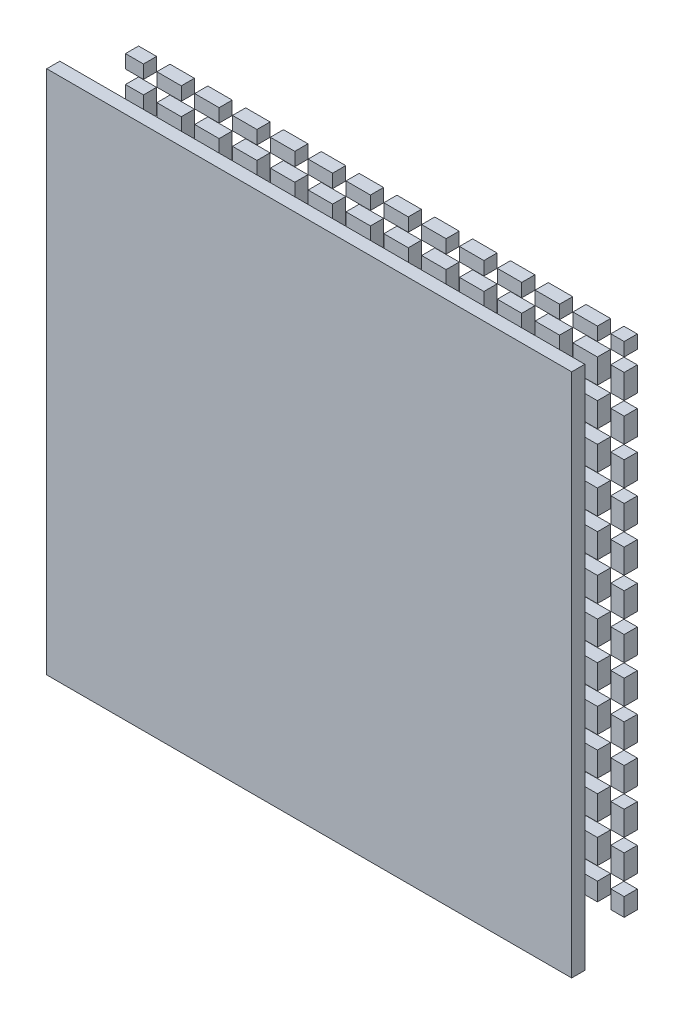
SolidWorks part; units mm, degrees
ref_plane "Front Plane" through (0, 0, 0) normal (0, 0, 1) x (1, 0, 0)
ref_plane "Top Plane" through (0, 0, 0) normal (0, 1, 0) x (1, 0, 0)
ref_plane "Right Plane" through (0, 0, 0) normal (1, 0, 0) x (0, 0, -1)
sketch "Sketch1" plane through (0, 0, 0) normal (0, 0, 1) x (1, 0, 0)
  line L0 (10, -8) -> (10, -9.5) construction
  line L1 (9.5, -9.5) -> (10, -9.5)
  line L2 (9.5, -9.5) -> (9.5, -8.9884)
  line L3 (9.5, -8.9884) -> (10, -8.9884)
  line L4 (10, -9.5) -> (10, -8.9884)
sketch "Sketch2" plane through (0, 0, 0) normal (0, 0, 1) x (1, 0, 0)
  line L0 (9.5, -9.5) -> (11.5, -9.5) construction
  line L1 (11.5, -9.5) -> (10.4047, -9.5) construction
  line L2 (9.5, -9.5) -> (9.5, -7.5) construction
  dimension "D1" = 2
  dimension "D2" = 2
ref_plane "Plane1" through (0, 0, 2) normal (0, 0, 1) x (1, 0, 0)
sketch "Sketch3" plane through (0, 0, 2) normal (0, 0, 1) x (1, 0, 0)
  line L1 (10, -10) -> (-10, -10)
  line L2 (10, -10) -> (10, 10)
  line L3 (10, 10) -> (-10, 10)
  line L4 (-10, -10) -> (-10, 10)
sketch "Sketch4" plane through (0, 0, 0) normal (0, 0, 1) x (1, 0, 0)
  line L1 (9.5, -9.5) -> (-9.5, -9.5)
  line L2 (9.5, -9.5) -> (9.5, 9.5)
  line L3 (9.5, 9.5) -> (-9.5, 9.5)
  line L4 (-9.5, -9.5) -> (-9.5, 9.5)
extrude "Boss-Extrude2" add sketch "Sketch4" against normal blind 0.5
extrude "Boss-Extrude3" add sketch "Sketch3" along normal blind 0.5 separate body
sketch "Sketch7" plane through (0, 0, -0.5) normal (0, 0, -1) x (-1, 0, 0)
  line L0 (-9.5, 9.5) -> (9.5, 9.5) construction
  line L1 (-8.99, 9.5) -> (-8.48, 9.5)
  line L2 (-8.99, 9.5) -> (-8.99, -9.5)
  line L3 (-8.99, -9.5) -> (-8.48, -9.5)
  line L4 (-8.48, 9.5) -> (-8.48, -9.5)
  line L5 (9.5, -9.5) -> (-9.5, -9.5) construction
  line L6 (-9.5, -9.5) -> (-9.5, 9.5) construction
  dimension "D1" = 0.51
  dimension "D2" = 0.51
extrude "Cut-Extrude2" cut sketch "Sketch7" against normal up to surface (0.5 mm away) and the other way through all up to face at (0, 0, 0)
pattern_linear "LPattern5" count 14 spacing 1.4412 along (-1, 0, 0) of "Cut-Extrude2"
sketch "Sketch9" plane through (0, 0, -0.5) normal (0, 0, -1) x (-1, 0, 0)
  line L0 (-9.5, -9.5) -> (-9.5, 9.5) construction
  line L1 (-9.5, 8.99) -> (9.5, 8.99)
  line L2 (-9.5, 8.99) -> (-9.5, 8.48)
  line L3 (-9.5, 8.48) -> (9.5, 8.48)
  line L4 (9.5, 8.99) -> (9.5, 8.48)
  line L5 (9.5, 9.5) -> (9.5, -9.5) construction
  line L6 (-9.5, 9.5) -> (-8.99, 9.5) construction
  point P10 (-9.245, 9.5)
  dimension "D1" = 0.51
  dimension "D2" = 0.51
extrude "Cut-Extrude3" cut sketch "Sketch9" against normal blind 0.5
pattern_linear "LPattern6" count 14 spacing 1.4412 along (0, -1, 0) of "Cut-Extrude3"
sketch "Sketch10" plane through (0, 0, 0) normal (0, 0, 1) x (1, 0, 0)
  line L0 (10, 10) -> (-10, 10) construction
  line L1 (-9.4943, 9.49) -> (9.49, 9.49) construction
  line L2 (-9.4943, 9.49) -> (-9.4943, -9.4943) construction
  line L3 (-9.4943, -9.4943) -> (9.49, -9.4943) construction
  line L4 (9.49, 9.49) -> (9.49, -9.4943) construction
  line L5 (10, -10) -> (10, 10) construction
  line L6 (-10, -10) -> (-10, 10) construction
  line L8 (-9.4943, 9.49) -> (-8.9843, 9.49)
  line L9 (-9.4943, 9.49) -> (-9.4943, 8.98)
  line L10 (-9.4943, 8.98) -> (-8.9843, 8.98)
  line L11 (-8.9843, 9.49) -> (-8.9843, 8.98)
  line L12 (-9.4943, -9.4943) -> (-8.9843, -9.4943)
  line L13 (-9.4943, -9.4943) -> (-9.4943, -8.9843)
  line L14 (-9.4943, -8.9843) -> (-8.9843, -8.9843)
  line L15 (-8.9843, -9.4943) -> (-8.9843, -8.9843)
  line L16 (9.49, -9.4943) -> (8.98, -9.4943)
  line L17 (9.49, -9.4943) -> (9.49, -8.9843)
  line L18 (9.49, -8.9843) -> (8.98, -8.9843)
  line L19 (8.98, -9.4943) -> (8.98, -8.9843)
  line L20 (9.49, 9.49) -> (8.98, 9.49)
  line L21 (9.49, 9.49) -> (9.49, 8.98)
  line L22 (9.49, 8.98) -> (8.98, 8.98)
  line L23 (8.98, 9.49) -> (8.98, 8.98)
  dimension "D1" = 0.51
  dimension "D2" = 0.51
  dimension "D3" = 0.5057
  dimension "D4" = 0.51
